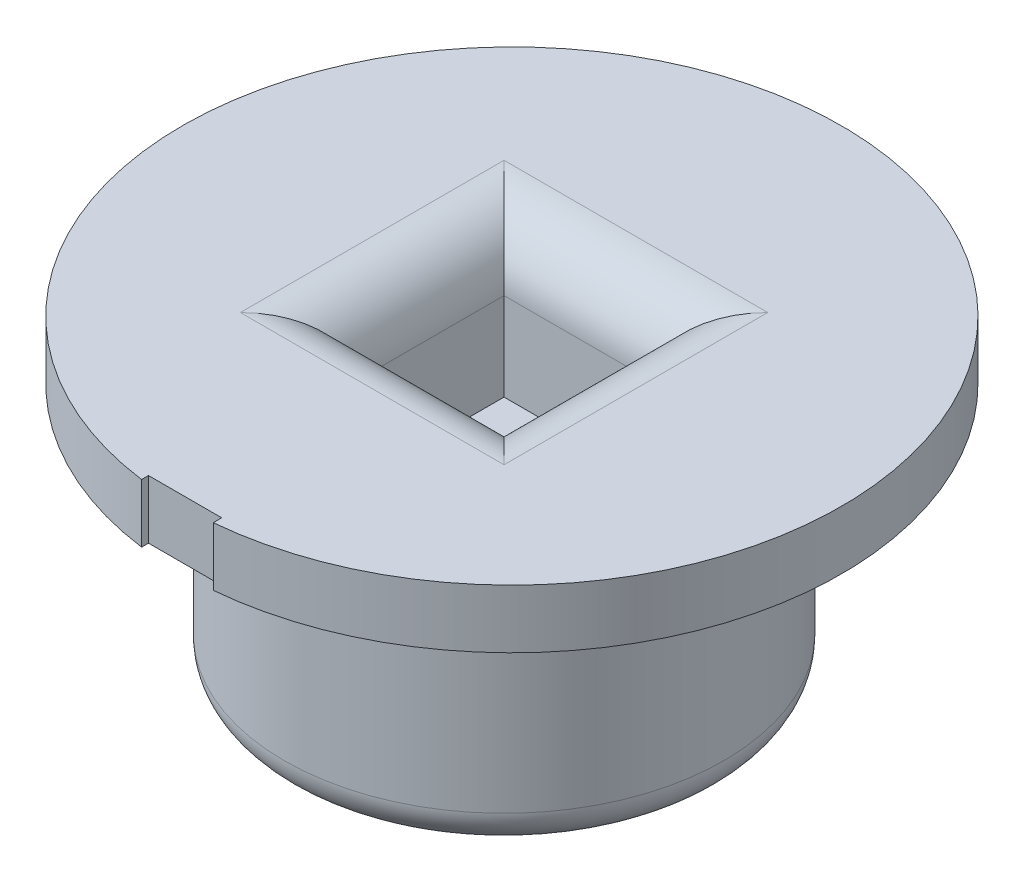
SolidWorks part; units mm, degrees
ref_plane "前视基准面" through (0, 0, 0) normal (0, 0, 1) x (1, 0, 0)
ref_plane "上视基准面" through (0, 0, 0) normal (0, 1, 0) x (1, 0, 0)
ref_plane "右视基准面" through (0, 0, 0) normal (1, 0, 0) x (0, 0, -1)
sketch "草图1" plane through (0, 0, 0) normal (0, 1, 0) x (1, 0, 0)
  circle A0 centre (0, 0) radius 3
  dimension "D1" = 6
extrude "凸台-拉伸1" add sketch "草图1" along normal blind 3.5 contours A0
sketch "草图2" plane through (0, 3.5, 0) normal (0, 1, 0) x (1, 0, 0)
  circle A0 centre (0.0949, 0.012) radius 4.5
  dimension "D1" = 9
extrude "凸台-拉伸2" add sketch "草图2" along normal blind 0.8
sketch "草图4" plane through (0, 4.3, 0) normal (0, 1, 0) x (1, 0, 0)
  line L1 (1, -1) -> (-1, -1)
  line L2 (1, -1) -> (1, 1)
  line L3 (1, 1) -> (-1, 1)
  line L4 (-1, -1) -> (-1, 1)
  line L5 (1, -1) -> (-1, 1) construction
  line L6 (1, 1) -> (-1, -1) construction
  circle A0 centre (0, 0) radius 3 construction
  point P0 (0, 0)
  dimension "D1" = 2
  dimension "D2" = 2
extrude "切除-拉伸1" cut sketch "草图4" against normal blind 2
fillet "圆角1" radius 0.5 1 edges at (0, 0, 3)
fillet "圆角2" radius 0.8 4 edges at (0, 4.3, 1) (-1, 4.3, 0) (0, 4.3, -1) (1, 4.3, 0)
sketch "草图5" plane through (0, 3.5, 0) normal (0, -1, 0) x (1, 0, 0)
  line L1 (-0.5, 5.0111) -> (0.5, 5.0111)
  line L2 (-0.5, 5.0111) -> (-0.5, 4.3544)
  line L3 (-0.5, 4.3544) -> (0.5, 4.3544)
  line L4 (0.5, 5.0111) -> (0.5, 4.3544)
  point P4 (0, 4.3544)
  point P6 (0, 0)
  point P7 (0, 0)
  point P8 (0, 0)
  point P9 (-0.6021, 4.3544)
  dimension "D1" = 0.6567
  dimension "D2" = 1
extrude "切除-拉伸2" cut sketch "草图5" against normal blind 1
